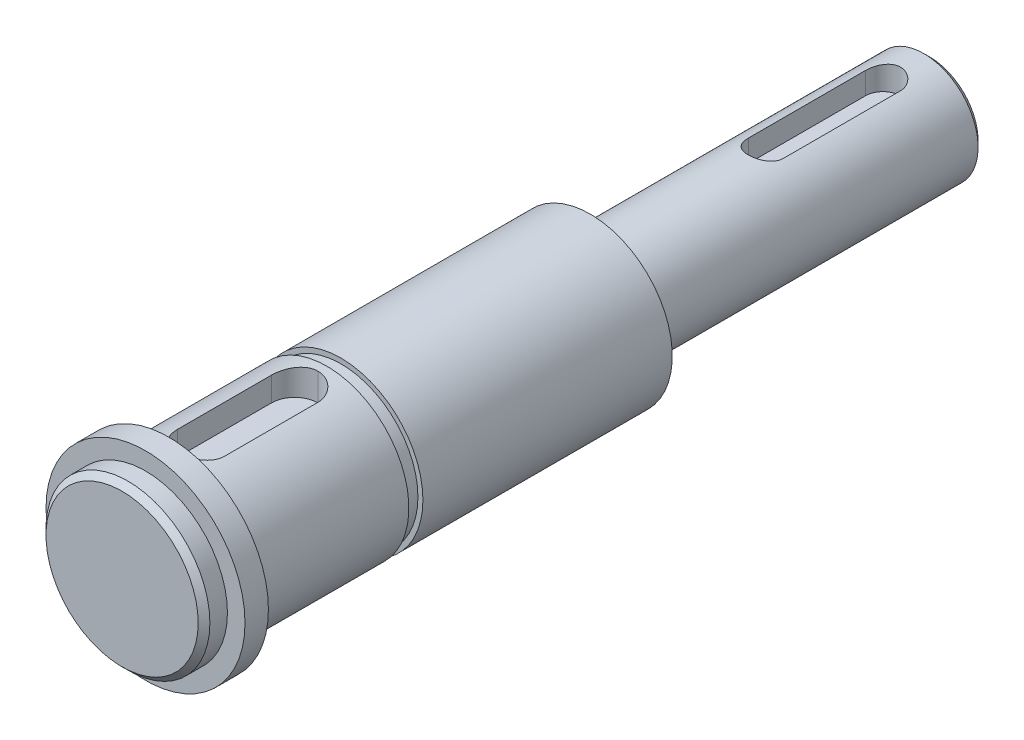
SolidWorks part; units mm, degrees
ref_plane "Ön Düzlem" through (0, 0, 0) normal (0, 0, 1) x (1, 0, 0)
ref_plane "Üst Düzlem" through (0, 0, 0) normal (0, 1, 0) x (1, 0, 0)
ref_plane "Sağ Düzlem" through (0, 0, 0) normal (1, 0, 0) x (0, 0, -1)
sketch "Sketch1" plane through (0, 0, 0) normal (0, 0, 1) x (1, 0, 0)
  circle A0 centre (0, 0) radius 14
  dimension "D1" = 28
extrude "Boss-Extrude1" add sketch "Sketch1" against normal blind 100 and the other way blind 5
sketch "Sketch2" plane through (0, 17.3, 0) normal (0, -1, 0) x (1, 0, 0)
  line L0 (14, 5) -> (-14, 5) construction
  line L1 (0, 5) -> (0, -1.5) construction
  line L8 (4, -1.5) -> (-4, -1.5)
  line L9 (-4, -1.5) -> (-4, -25.5)
  line L11 (4, -25.5) -> (4, -1.5)
  line L47 (-4, -25.5) -> (4, -25.5)
  dimension "D1" = 8
  dimension "D2" = 24
  dimension "D3" = 6.5
extrude "Cut-Extrude1" cut sketch "Sketch2" along normal blind 8
sketch "Sketch3" plane through (0, 0, 5) normal (0, 0, 1) x (1, 0, 0)
  circle A0 centre (0, 0) radius 14
extrude "Boss-Extrude2" add sketch "Sketch3" along normal blind 8
fillet "Fillet1" radius 4 4 edges at (-4, 11.3582, -25.5) (4, 11.3582, -25.5) (4, 11.3582, -1.5) (-4, 11.3582, -1.5)
sketch "Sketch4" plane through (0, 0, 0) normal (1, 0, 0) x (0, 0, -1)
  line L1 (0, -17) -> (-4, -17)
  line L2 (0, -17) -> (0, -14)
  line L3 (0, -14) -> (-4, -14)
  line L4 (-4, -17) -> (-4, -14)
  line L6 (0, 0) -> (45.6083, 0) construction
  dimension "D1" = 4
  dimension "D2" = 17
revolve "Revolve1" add sketch "Sketch4" angle 360 about L6
sketch "Sketch7" plane through (0, 0, 0) normal (0, 1, 0) x (1, 0, 0)
  line L2 (-13.15, 29.3973) -> (-13.15, 26.9973)
  line L3 (-13.15, 26.9973) -> (-20, 26.9973)
  line L4 (-20, 26.9973) -> (-20, 29.3973)
  line L5 (-20, 29.3973) -> (-13.15, 29.3973)
  dimension "D1" = 2.4
revolve "Cut-Revolve2" cut sketch "Sketch7" angle 360 about axis through (0, 0, 5) along (0, 0, -1)
sketch "Sketch8" plane through (0, 0, 13) normal (0, 0, 1) x (1, 0, 0)
  circle A1 centre (0, 0) radius 14
  circle A2 centre (0, 0) radius 14
  dimension "D1" = 0
extrude "Cut-Extrude2" cut sketch "Sketch8" against normal blind 5
sketch "Sketch9" plane through (0, 0, -100) normal (0, 0, -1) x (-1, 0, 0)
  circle A0 centre (0, 0) radius 9.25
  circle A1 centre (0, 0) radius 21.9369
  dimension "D1" = 18.5
extrude "Cut-Extrude3" cut sketch "Sketch9" against normal blind 28
sketch "Sketch10" plane through (0, 0, -100) normal (0, 0, -1) x (-1, 0, 0)
  circle A0 centre (0, 0) radius 9.25 construction
  circle A1 centre (0, 0) radius 9.25
extrude "Boss-Extrude3" add sketch "Sketch10" along normal blind 30
chamfer "Chamfer1" distance 1 angle 45 2 edges at (14, 0, 8) (-9.25, 0, -130)
sketch "Sketch12" plane through (0, 0, -130) normal (0, 0, -1) x (-1, 0, 0)
  line L0 (0, 0) -> (-12.1633, 10.2272) construction
ref_plane "Plane2" through (0, 0, 0) normal (-0.6436, 0.7654, 0) x (0.7654, 0.6436, 0)
sketch "Sketch15" plane through (0, 0, 0) normal (0, 1, 0) x (1, 0, 0)
  line L0 (0, 122) -> (0, 102) construction
  line L1 (3, 122) -> (3, 102)
  line L2 (-3, 122) -> (-3, 102)
  line L3 (8.25, 130) -> (-8.25, 130) construction
  arc A0 (3, 122) -> (-3, 122) centre (0, 122) ccw
  arc A1 (-3, 102) -> (3, 102) centre (0, 102) ccw
  point P3 (0, 112)
  dimension "D1" = 8
  dimension "D2" = 3
  dimension "D3" = 20
extrude "Cut-Extrude4" cut sketch "Sketch15" along normal blind 10 from offset 5
